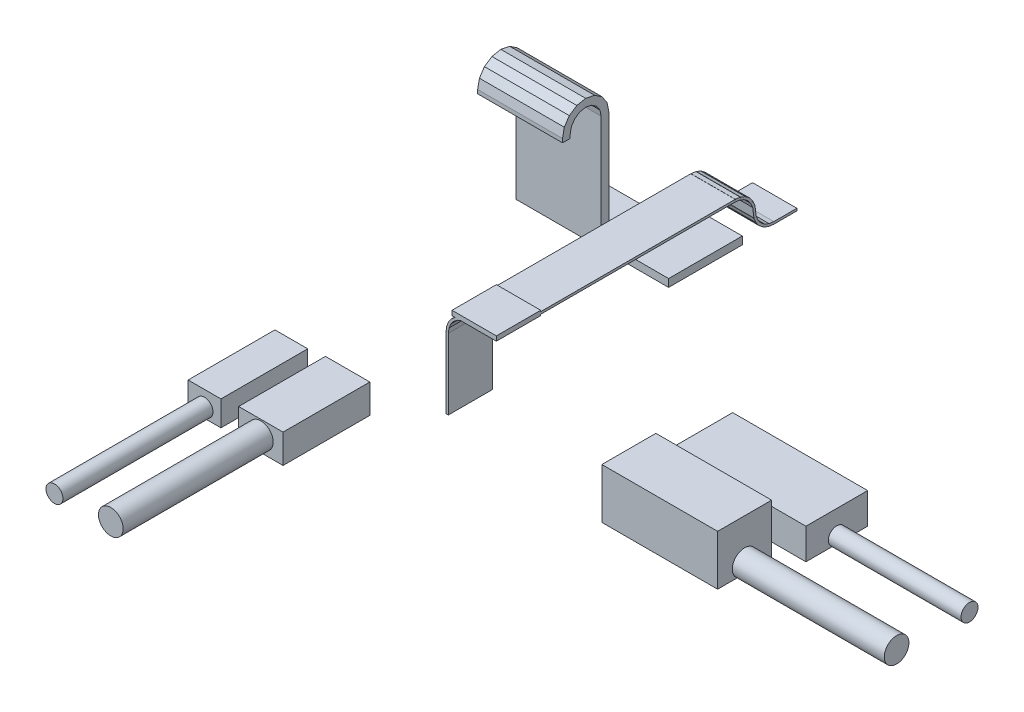
SolidWorks part; units mm, degrees
ref_plane "Front Plane" through (0, 0, 0) normal (0, 0, 1) x (1, 0, 0)
ref_plane "Top Plane" through (0, 0, 0) normal (0, 1, 0) x (1, 0, 0)
ref_plane "Right Plane" through (0, 0, 0) normal (1, 0, 0) x (0, 0, -1)
ref_plane "PY93" through (0, 0, 93) normal (0, 0, 1) x (1, 0, 0)
sketch "Sketch1" plane through (0, 0, 93) normal (0, 0, 1) x (1, 0, 0)
  line L0 (-48.05, -18.05) -> (-39.55, -18.05)
  line L1 (-39.55, -18.05) -> (-39.55, -11.55)
  line L2 (-39.55, -11.55) -> (-48.05, -11.55)
  line L3 (-48.05, -11.55) -> (-48.05, -18.05)
extrude "Plug usbc" add sketch "Sketch1" along normal blind 22.5
ref_plane "PY115" through (0, 0, 115) normal (0, 0, 1) x (1, 0, 0)
sketch "Sketch2" plane through (0, 0, 115) normal (0, 0, 1) x (1, 0, 0)
  circle A0 centre (-43.8, -15.5) radius 2.2
extrude "Cable usbc" add sketch "Sketch2" along normal blind 39.4
sketch "Sketch3" plane through (0, 0, 93) normal (0, 0, 1) x (1, 0, 0)
  line L0 (-34.95, -18.45) -> (-23.45, -18.45)
  line L1 (-23.45, -18.45) -> (-23.45, -10.95)
  line L2 (-23.45, -10.95) -> (-34.95, -10.95)
  line L3 (-34.95, -10.95) -> (-34.95, -18.45)
extrude "Plug hdmi" add sketch "Sketch3" along normal blind 22.5
sketch "Sketch4" plane through (0, 0, 115) normal (0, 0, 1) x (1, 0, 0)
  circle A0 centre (-29.2, -14.5) radius 3.2
extrude "Cable hdmi" add sketch "Sketch4" along normal blind 39.4
ref_plane "PX33" through (33, 0, 0) normal (1, 0, 0) x (0, 0, -1)
sketch "Sketch5" plane through (33, 0, 0) normal (1, 0, 0) x (0, 0, -1)
  line L0 (-89.3, -16.1) -> (-75.3, -16.1)
  line L1 (-75.3, -16.1) -> (-75.3, -3.1)
  line L2 (-75.3, -3.1) -> (-89.3, -3.1)
  line L3 (-89.3, -3.1) -> (-89.3, -16.1)
extrude "Plug eth" add sketch "Sketch5" along normal blind 30
ref_plane "PX62_5" through (62.5, 0, 0) normal (1, 0, 0) x (0, 0, -1)
sketch "Sketch6" plane through (62.5, 0, 0) normal (1, 0, 0) x (0, 0, -1)
  circle A0 centre (-82.3, -13.5) radius 3.2
extrude "Cable eth" add sketch "Sketch6" along normal blind 39.9
sketch "Sketch7" plane through (33, 0, 0) normal (1, 0, 0) x (0, 0, -1)
  line L0 (-71.4, -16.4) -> (-55.4, -16.4)
  line L1 (-55.4, -16.4) -> (-55.4, -8.4)
  line L2 (-55.4, -8.4) -> (-71.4, -8.4)
  line L3 (-71.4, -8.4) -> (-71.4, -16.4)
extrude "Plug usba" add sketch "Sketch7" along normal blind 35
ref_plane "PX67_5" through (67.5, 0, 0) normal (1, 0, 0) x (0, 0, -1)
sketch "Sketch8" plane through (67.5, 0, 0) normal (1, 0, 0) x (0, 0, -1)
  circle A0 centre (-63.4, -14.5) radius 2.2
extrude "Cable usba" add sketch "Sketch8" along normal blind 34.9
ref_plane "PXm5_35" through (-5.35, 0, 0) normal (1, 0, 0) x (0, 0, -1)
sketch "Sketch9" plane through (-5.35, 0, 0) normal (1, 0, 0) x (0, 0, -1)
  line L0 (-11.9, 1.7) -> (-17.9, 1.7)
  line L1 (-17.9, 1.7) -> (-17.9, 2.3)
  line L2 (-17.9, 2.3) -> (-11.9, 2.3)
  line L3 (-11.9, 2.3) -> (-11.9, 1.7)
extrude "Ribbon 0" add sketch "Sketch9" along normal blind 11.5
sketch "Sketch10" plane through (-5.35, 0, 0) normal (1, 0, 0) x (0, 0, -1)
  line L0 (-17.9392, 1.7026) -> (-19.2333, 1.8729)
  line L1 (-19.2333, 1.8729) -> (-19.1549, 2.4678)
  line L2 (-19.1549, 2.4678) -> (-17.8608, 2.2974)
  line L3 (-17.8608, 2.2974) -> (-17.9392, 1.7026)
extrude "Ribbon 1" add sketch "Sketch10" along normal blind 11.5
sketch "Sketch11" plane through (-5.35, 0, 0) normal (1, 0, 0) x (0, 0, -1)
  line L0 (-19.3089, 1.8932) -> (-20.5148, 2.3927)
  line L1 (-20.5148, 2.3927) -> (-20.2852, 2.947)
  line L2 (-20.2852, 2.947) -> (-19.0793, 2.4475)
  line L3 (-19.0793, 2.4475) -> (-19.3089, 1.8932)
extrude "Ribbon 2" add sketch "Sketch11" along normal blind 11.5
sketch "Sketch12" plane through (-5.35, 0, 0) normal (1, 0, 0) x (0, 0, -1)
  line L0 (-20.5826, 2.4319) -> (-21.6182, 3.2265)
  line L1 (-21.6182, 3.2265) -> (-21.2529, 3.7025)
  line L2 (-21.2529, 3.7025) -> (-20.2174, 2.9079)
  line L3 (-20.2174, 2.9079) -> (-20.5826, 2.4319)
extrude "Ribbon 3" add sketch "Sketch12" along normal blind 11.5
sketch "Sketch13" plane through (-5.35, 0, 0) normal (1, 0, 0) x (0, 0, -1)
  line L0 (-21.6735, 3.2818) -> (-22.4681, 4.3174)
  line L1 (-22.4681, 4.3174) -> (-21.9921, 4.6826)
  line L2 (-21.9921, 4.6826) -> (-21.1975, 3.6471)
  line L3 (-21.1975, 3.6471) -> (-21.6735, 3.2818)
extrude "Ribbon 4" add sketch "Sketch13" along normal blind 11.5
sketch "Sketch14" plane through (-5.35, 0, 0) normal (1, 0, 0) x (0, 0, -1)
  line L0 (-22.5073, 4.3852) -> (-23.0068, 5.5911)
  line L1 (-23.0068, 5.5911) -> (-22.4525, 5.8207)
  line L2 (-22.4525, 5.8207) -> (-21.953, 4.6148)
  line L3 (-21.953, 4.6148) -> (-22.5073, 4.3852)
extrude "Ribbon 5" add sketch "Sketch14" along normal blind 11.5
sketch "Sketch15" plane through (-5.35, 0, 0) normal (1, 0, 0) x (0, 0, -1)
  line L0 (-23.0271, 5.6667) -> (-23.1974, 6.9608)
  line L1 (-23.1974, 6.9608) -> (-22.6026, 7.0392)
  line L2 (-22.6026, 7.0392) -> (-22.4322, 5.7451)
  line L3 (-22.4322, 5.7451) -> (-23.0271, 5.6667)
extrude "Ribbon 6" add sketch "Sketch15" along normal blind 11.5
sketch "Sketch16" plane through (-5.35, 0, 0) normal (1, 0, 0) x (0, 0, -1)
  line L0 (-23.1974, 6.9608) -> (-23.3678, 8.2549)
  line L1 (-23.3678, 8.2549) -> (-22.7729, 8.3333)
  line L2 (-22.7729, 8.3333) -> (-22.6026, 7.0392)
  line L3 (-22.6026, 7.0392) -> (-23.1974, 6.9608)
extrude "Ribbon 7" add sketch "Sketch16" along normal blind 11.5
sketch "Sketch17" plane through (-5.35, 0, 0) normal (1, 0, 0) x (0, 0, -1)
  line L0 (-23.3475, 8.1793) -> (-23.847, 9.3852)
  line L1 (-23.847, 9.3852) -> (-23.2927, 9.6148)
  line L2 (-23.2927, 9.6148) -> (-22.7932, 8.4089)
  line L3 (-22.7932, 8.4089) -> (-23.3475, 8.1793)
extrude "Ribbon 8" add sketch "Sketch17" along normal blind 11.5
sketch "Sketch18" plane through (-5.35, 0, 0) normal (1, 0, 0) x (0, 0, -1)
  line L0 (-23.8079, 9.3174) -> (-24.6025, 10.3529)
  line L1 (-24.6025, 10.3529) -> (-24.1265, 10.7182)
  line L2 (-24.1265, 10.7182) -> (-23.3319, 9.6826)
  line L3 (-23.3319, 9.6826) -> (-23.8079, 9.3174)
extrude "Ribbon 9" add sketch "Sketch18" along normal blind 11.5
sketch "Sketch19" plane through (-5.35, 0, 0) normal (1, 0, 0) x (0, 0, -1)
  line L0 (-24.5471, 10.2975) -> (-25.5826, 11.0921)
  line L1 (-25.5826, 11.0921) -> (-25.2174, 11.5681)
  line L2 (-25.2174, 11.5681) -> (-24.1818, 10.7735)
  line L3 (-24.1818, 10.7735) -> (-24.5471, 10.2975)
extrude "Ribbon 10" add sketch "Sketch19" along normal blind 11.5
sketch "Sketch20" plane through (-5.35, 0, 0) normal (1, 0, 0) x (0, 0, -1)
  line L0 (-25.5148, 11.053) -> (-26.7207, 11.5525)
  line L1 (-26.7207, 11.5525) -> (-26.4911, 12.1068)
  line L2 (-26.4911, 12.1068) -> (-25.2852, 11.6073)
  line L3 (-25.2852, 11.6073) -> (-25.5148, 11.053)
extrude "Ribbon 11" add sketch "Sketch20" along normal blind 11.5
sketch "Sketch21" plane through (-5.35, 0, 0) normal (1, 0, 0) x (0, 0, -1)
  line L0 (-26.6451, 11.5322) -> (-27.9392, 11.7026)
  line L1 (-27.9392, 11.7026) -> (-27.8608, 12.2974)
  line L2 (-27.8608, 12.2974) -> (-26.5667, 12.1271)
  line L3 (-26.5667, 12.1271) -> (-26.6451, 11.5322)
extrude "Ribbon 12" add sketch "Sketch21" along normal blind 11.5
sketch "Sketch22" plane through (-5.35, 0, 0) normal (1, 0, 0) x (0, 0, -1)
  line L0 (-27.9, 11.7) -> (-84.05, 11.7)
  line L1 (-84.05, 11.7) -> (-84.05, 12.3)
  line L2 (-84.05, 12.3) -> (-27.9, 12.3)
  line L3 (-27.9, 12.3) -> (-27.9, 11.7)
extrude "Ribbon 13" add sketch "Sketch22" along normal blind 11.5
ref_plane "PZ11_4" through (0, 11.4, 0) normal (0, 1, 0) x (1, 0, 0)
sketch "Sketch23" plane through (0, 11.4, 0) normal (0, 1, 0) x (1, 0, 0)
  line L0 (-5.35, -89.8) -> (6.15, -89.8)
  line L1 (6.15, -89.8) -> (6.15, -78.3)
  line L2 (6.15, -78.3) -> (-5.35, -78.3)
  line L3 (-5.35, -78.3) -> (-5.35, -89.8)
extrude "Ribbon Fold" add sketch "Sketch23" along normal blind 1.2
ref_plane "PY78_3" through (0, 0, 78.3) normal (0, 0, 1) x (1, 0, 0)
sketch "Sketch24" plane through (0, 0, 78.3) normal (0, 0, 1) x (1, 0, 0)
  line L0 (0.4, 11.7) -> (-1.6, 11.7)
  line L1 (-1.6, 11.7) -> (-1.6, 12.3)
  line L2 (-1.6, 12.3) -> (0.4, 12.3)
  line L3 (0.4, 12.3) -> (0.4, 11.7)
extrude "Ribbon 14" add sketch "Sketch24" along normal blind 11.5
sketch "Sketch25" plane through (0, 0, 78.3) normal (0, 0, 1) x (1, 0, 0)
  line L0 (-1.5608, 11.7026) -> (-2.8549, 11.5322)
  line L1 (-2.8549, 11.5322) -> (-2.9333, 12.1271)
  line L2 (-2.9333, 12.1271) -> (-1.6392, 12.2974)
  line L3 (-1.6392, 12.2974) -> (-1.5608, 11.7026)
extrude "Ribbon 15" add sketch "Sketch25" along normal blind 11.5
sketch "Sketch26" plane through (0, 0, 78.3) normal (0, 0, 1) x (1, 0, 0)
  line L0 (-2.7793, 11.5525) -> (-3.9852, 11.053)
  line L1 (-3.9852, 11.053) -> (-4.2148, 11.6073)
  line L2 (-4.2148, 11.6073) -> (-3.0089, 12.1068)
  line L3 (-3.0089, 12.1068) -> (-2.7793, 11.5525)
extrude "Ribbon 16" add sketch "Sketch26" along normal blind 11.5
sketch "Sketch27" plane through (0, 0, 78.3) normal (0, 0, 1) x (1, 0, 0)
  line L0 (-3.9174, 11.0921) -> (-4.9529, 10.2975)
  line L1 (-4.9529, 10.2975) -> (-5.3182, 10.7735)
  line L2 (-5.3182, 10.7735) -> (-4.2826, 11.5681)
  line L3 (-4.2826, 11.5681) -> (-3.9174, 11.0921)
extrude "Ribbon 17" add sketch "Sketch27" along normal blind 11.5
sketch "Sketch28" plane through (0, 0, 78.3) normal (0, 0, 1) x (1, 0, 0)
  line L0 (-4.8975, 10.3529) -> (-5.6921, 9.3174)
  line L1 (-5.6921, 9.3174) -> (-6.1681, 9.6826)
  line L2 (-6.1681, 9.6826) -> (-5.3735, 10.7182)
  line L3 (-5.3735, 10.7182) -> (-4.8975, 10.3529)
extrude "Ribbon 18" add sketch "Sketch28" along normal blind 11.5
sketch "Sketch29" plane through (0, 0, 78.3) normal (0, 0, 1) x (1, 0, 0)
  line L0 (-5.653, 9.3852) -> (-6.1525, 8.1793)
  line L1 (-6.1525, 8.1793) -> (-6.7068, 8.4089)
  line L2 (-6.7068, 8.4089) -> (-6.2073, 9.6148)
  line L3 (-6.2073, 9.6148) -> (-5.653, 9.3852)
extrude "Ribbon 19" add sketch "Sketch29" along normal blind 11.5
sketch "Sketch30" plane through (0, 0, 78.3) normal (0, 0, 1) x (1, 0, 0)
  line L0 (-6.1322, 8.2549) -> (-6.3026, 6.9608)
  line L1 (-6.3026, 6.9608) -> (-6.8974, 7.0392)
  line L2 (-6.8974, 7.0392) -> (-6.7271, 8.3333)
  line L3 (-6.7271, 8.3333) -> (-6.1322, 8.2549)
extrude "Ribbon 20" add sketch "Sketch30" along normal blind 11.5
sketch "Sketch31" plane through (0, 0, 78.3) normal (0, 0, 1) x (1, 0, 0)
  line L0 (-6.3, 7) -> (-6.3, -11.39)
  line L1 (-6.3, -11.39) -> (-6.9, -11.39)
  line L2 (-6.9, -11.39) -> (-6.9, 7)
  line L3 (-6.9, 7) -> (-6.3, 7)
extrude "Ribbon 21" add sketch "Sketch31" along normal blind 11.5
ref_plane "PZm13" through (0, -13, 0) normal (0, 1, 0) x (1, 0, 0)
sketch "Sketch32" plane through (0, -13, 0) normal (0, 1, 0) x (1, 0, 0)
  line L0 (-18, -17.9) -> (-8, -17.9)
  line L1 (-8, -17.9) -> (-8, -11.9)
  line L2 (-8, -11.9) -> (-18, -11.9)
  line L3 (-18, -11.9) -> (-18, -17.9)
extrude "Jumpers Window" add sketch "Sketch32" along normal blind 2
sketch "Sketch33" plane through (0, -13, 0) normal (0, 1, 0) x (1, 0, 0)
  line L0 (-47.5, -31) -> (-8, -31)
  line L1 (-8, -31) -> (-8, -17.9)
  line L2 (-8, -17.9) -> (-47.5, -17.9)
  line L3 (-47.5, -17.9) -> (-47.5, -31)
extrude "Jumpers Across" add sketch "Sketch33" along normal blind 2
ref_plane "PXm47_5" through (-47.5, 0, 0) normal (1, 0, 0) x (0, 0, -1)
sketch "Sketch34" plane through (-47.5, 0, 0) normal (1, 0, 0) x (0, 0, -1)
  line L0 (-31, -13) -> (-29, -13)
  line L1 (-29, -13) -> (-29, 16.7)
  line L2 (-29, 16.7) -> (-31, 16.7)
  line L3 (-31, 16.7) -> (-31, -13)
extrude "Jumpers Rise" add sketch "Sketch34" along normal blind 22
sketch "Sketch35" plane through (-47.5, 0, 0) normal (1, 0, 0) x (0, 0, -1)
  line L0 (-29, 16.7) -> (-29.4567, 18.9961)
  line L1 (-29.4567, 18.9961) -> (-30.7574, 20.9426)
  line L2 (-30.7574, 20.9426) -> (-32.7039, 22.2433)
  line L3 (-32.7039, 22.2433) -> (-35, 22.7)
  line L4 (-35, 22.7) -> (-37.2961, 22.2433)
  line L5 (-37.2961, 22.2433) -> (-39.2426, 20.9426)
  line L6 (-39.2426, 20.9426) -> (-40.5433, 18.9961)
  line L7 (-40.5433, 18.9961) -> (-41, 16.7)
  line L8 (-41, 16.7) -> (-39, 16.7)
  line L9 (-39, 16.7) -> (-38.6955, 18.2307)
  line L10 (-38.6955, 18.2307) -> (-37.8284, 19.5284)
  line L11 (-37.8284, 19.5284) -> (-36.5307, 20.3955)
  line L12 (-36.5307, 20.3955) -> (-35, 20.7)
  line L13 (-35, 20.7) -> (-33.4693, 20.3955)
  line L14 (-33.4693, 20.3955) -> (-32.1716, 19.5284)
  line L15 (-32.1716, 19.5284) -> (-31.3045, 18.2307)
  line L16 (-31.3045, 18.2307) -> (-31, 16.7)
  line L17 (-31, 16.7) -> (-29, 16.7)
extrude "Jumpers Hairpin" add sketch "Sketch35" along normal blind 22
sketch "Sketch36" plane through (-47.5, 0, 0) normal (1, 0, 0) x (0, 0, -1)
  line L0 (-41, 15.71) -> (-39, 15.71)
  line L1 (-39, 15.71) -> (-39, 16.7)
  line L2 (-39, 16.7) -> (-41, 16.7)
  line L3 (-41, 16.7) -> (-41, 15.71)
extrude "Jumpers Into Housings" add sketch "Sketch36" along normal blind 22
